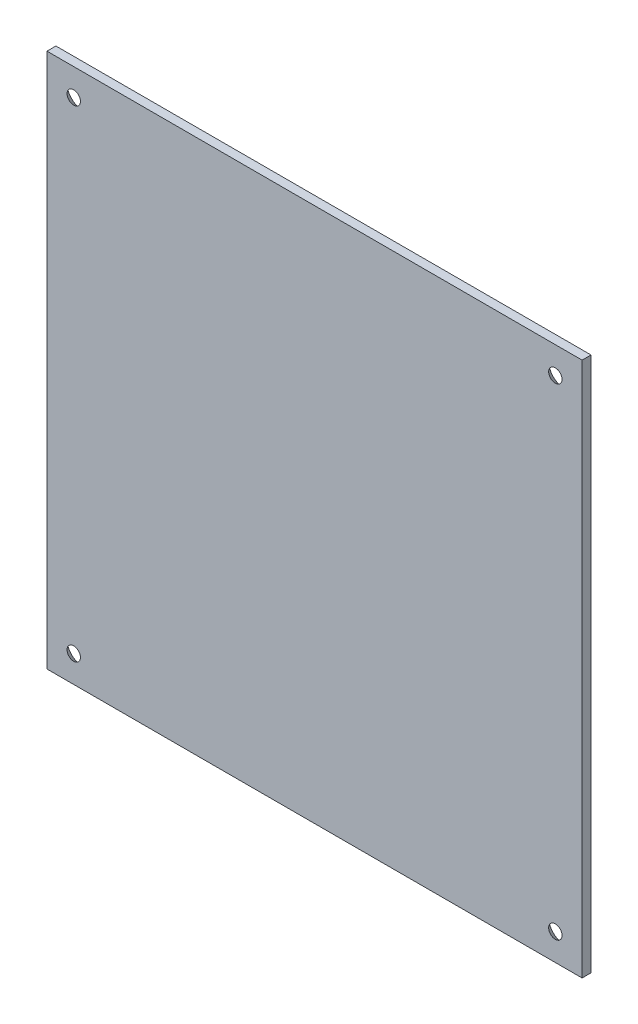
SolidWorks part; units mm, degrees
ref_plane "Front" through (0, 0, 0) normal (0, 0, 1) x (1, 0, 0)
ref_plane "Top" through (0, 0, 0) normal (0, 1, 0) x (1, 0, 0)
ref_plane "Right" through (0, 0, 0) normal (1, 0, 0) x (0, 0, -1)
sketch "Sketch1" plane through (0, 0, 0) normal (0, 0, 1) x (1, 0, 0)
  line L1 (-25.6041, 14.6909) -> (94.3959, 14.6909)
  line L2 (-25.6041, 14.6909) -> (-25.6041, -105.3091)
  line L3 (-25.6041, -105.3091) -> (94.3959, -105.3091)
  line L4 (94.3959, 14.6909) -> (94.3959, -105.3091)
  dimension "D1" = 120
  dimension "D2" = 120
extrude "Boss-Extrude1" add sketch "Sketch1" along normal blind 2
sketch "Sketch2" plane through (0, 0, 0) normal (0, 0, -1) x (-1, 0, 0)
  line L0 (-94.3959, -45.3091) -> (-43.435, -45.3091) construction
  line L1 (-94.3959, -105.3091) -> (-94.3959, 14.6909) construction
  line L2 (-34.3959, -105.3091) -> (-34.3959, -72.5582) construction
  line L3 (25.6041, -105.3091) -> (-94.3959, -105.3091) construction
  circle A0 centre (-88.3959, -99.3091) radius 1.5
  circle A1 centre (19.6041, -99.3091) radius 1.5
  circle A2 centre (19.6041, 8.6909) radius 1.5
  circle A3 centre (-88.3959, 8.6909) radius 1.5
  point P12 (-87.5761, -105.3091)
  dimension "D1" = 3
  dimension "D2" = 6
  dimension "D3" = 6
extrude "Cut-Extrude1" cut sketch "Sketch2" against normal blind 3
chamfer "Chamfer1" distance 2 angle 45 4 edges at (-21.1041, 8.6909, 0) (-18.1041, -99.3091, 0) (86.8959, -99.3091, 0) (89.8959, 8.6909, 0)
